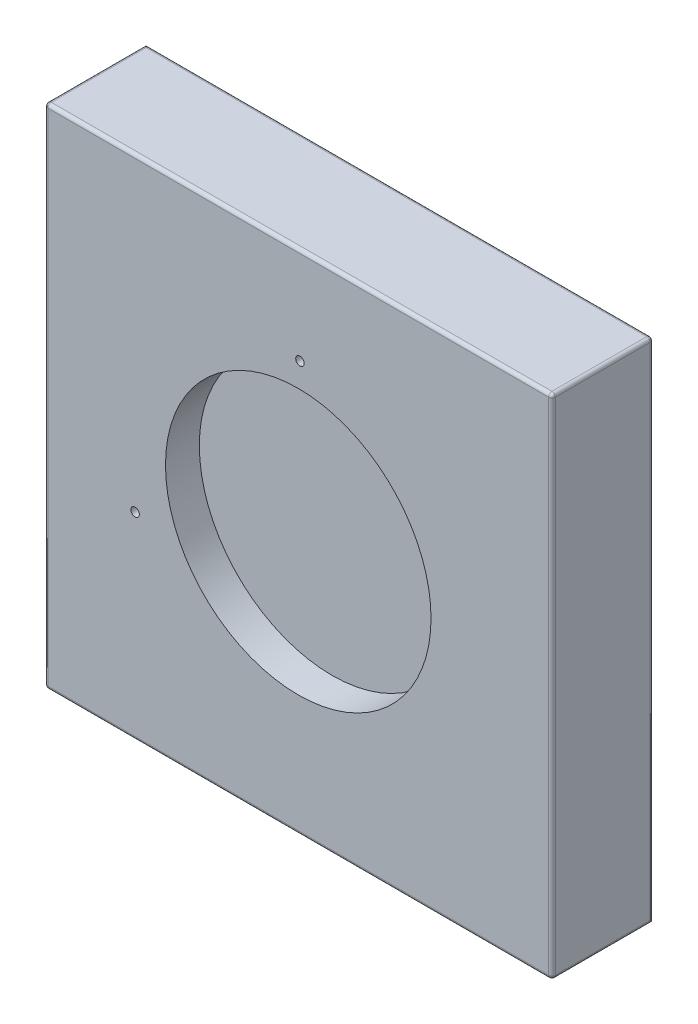
SolidWorks part; units mm, degrees
material "PLA"
ref_plane "Front Plane" through (0, 0, 0) normal (0, 0, 1) x (1, 0, 0)
ref_plane "Top Plane" through (0, 0, 0) normal (0, 1, 0) x (1, 0, 0)
ref_plane "Right Plane" through (0, 0, 0) normal (1, 0, 0) x (0, 0, -1)
sketch "Sketch1" plane through (0, 0, 0) normal (0, 0, 1) x (1, 0, 0)
  line L1 (-75, -75) -> (75, -75)
  line L2 (-75, -75) -> (-75, 75)
  line L3 (-75, 75) -> (75, 75)
  line L4 (75, -75) -> (75, 75)
  line L5 (-75, -75) -> (75, 75) construction
  line L6 (-75, 75) -> (75, -75) construction
  point P0 (0, 0)
  dimension "D1" = 150
  dimension "D2" = 150
extrude "Boss-Extrude1" add sketch "Sketch1" against normal blind 30 contours L2 L3 L4 L1
sketch "Sketch2" plane through (0, 0, 0) normal (0, 0, 1) x (1, 0, 0)
  circle A0 centre (0, 0) radius 39.25
  dimension "D1" = 78.5
fillet "Fillet1" radius 1 10 edges at (75, -75, -15) (-75, -75, -15) (-75, 75, -15) (75, 0, -30) (0, 75, -30) (75, 75, -15) (0, -75, 0) (-75, 0, 0) (75, 0, 0) (0, 75, 0)
sketch "Sketch7" plane through (0, 0, 0) normal (0, 1, 0) x (1, 0, 0)
  line L1 (-39.7685, 40.3246) -> (-29.7685, 40.3246)
  line L2 (-39.7685, 40.3246) -> (-39.7685, 30.3246)
  line L3 (-39.7685, 30.3246) -> (-29.7685, 30.3246)
  line L4 (-29.7685, 40.3246) -> (-29.7685, 30.3246)
  dimension "D1" = 10
  dimension "D2" = 10
ref_axis "Axis2" through (0, 0, 0) along (0, 0, -1)
extrude "Cut-Extrude4" cut sketch "Sketch2" against normal blind 10 contours A0
sketch "Sketch18" plane through (0, 0, 0) normal (0, 0, 1) x (1, 0, 0)
  circle A0 centre (0.4962, 46.5) radius 2.475
  circle A1 centre (-48.2375, -16.5473) radius 2.475
hole_wizard "Tap Drill for M3x0.5 Tap3" positions "Sketch19" profile "Sketch20" hole size "M3x0.5" standard "ANSI Metric"
sketch "Sketch19" plane through (0, 0, 0) normal (0, 0, 1) x (1, 0, 0)
  point P0 (0.4962, 46.5)
  point P3 (-48.2375, -16.5473)
sketch "Sketch20" plane through (0.4962, 46.5, 0) normal (1, 0, 0) x (0, -1, 0)
  line L0 (0, 0) -> (0, 10.7511)
  line L1 (0, 10.7511) -> (1.25, 10)
  line L2 (1.25, 10) -> (1.25, 0)
  line L5 (1.25, 0) -> (0, 0)
  line L10 (0, 10.7511) -> (-1.25, 10) construction
  line L11 (0, -6.35) -> (0, 107.95) construction
  dimension "Hole Dia." = 2.5
  dimension "Hole Depth" = 10
  dimension "Drill Angle" = 118
